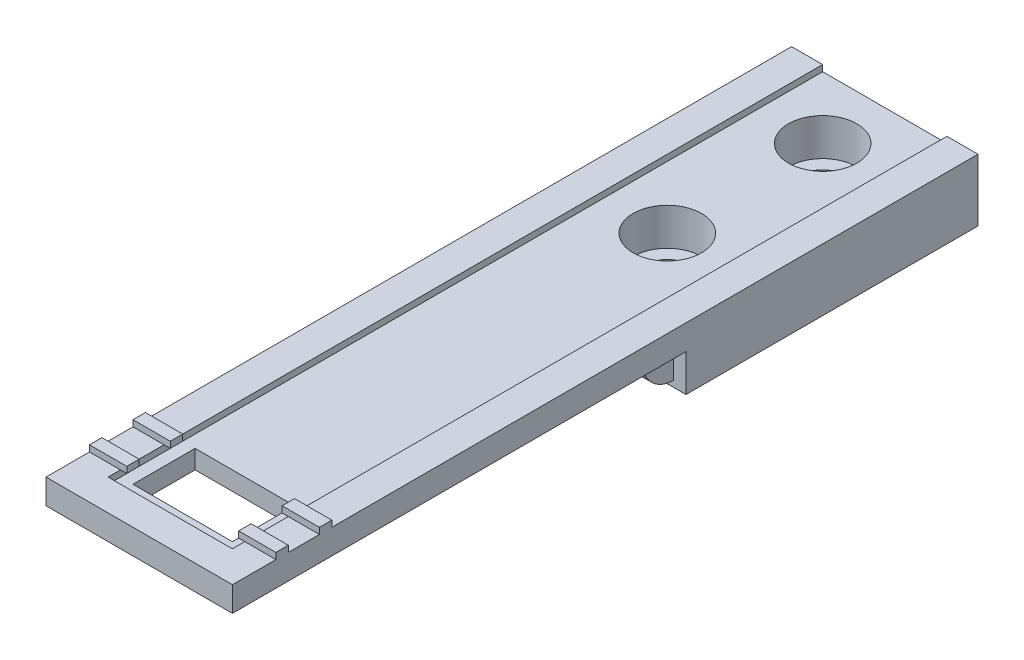
SolidWorks part; units mm, degrees
ref_plane "Front Plane" through (0, 0, 0) normal (0, 0, 1) x (1, 0, 0)
ref_plane "Top Plane" through (0, 0, 0) normal (0, 1, 0) x (1, 0, 0)
ref_plane "Right Plane" through (0, 0, 0) normal (1, 0, 0) x (0, 0, -1)
sketch "Sketch1" plane through (0, 0, 0) normal (0, 1, 0) x (1, 0, 0)
  line L1 (-12.8623, 1.9673) -> (17.1377, 1.9673)
  line L2 (-12.8623, 1.9673) -> (-12.8623, -118.0327)
  line L3 (-12.8623, -118.0327) -> (17.1377, -118.0327)
  line L4 (17.1377, 1.9673) -> (17.1377, -118.0327)
  dimension "D1" = 30
  dimension "D2" = 120
extrude "Boss-Extrude1" add sketch "Sketch1" along normal blind 9
sketch "Sketch2" plane through (0, 9, 0) normal (0, 1, 0) x (1, 0, 0)
  line L0 (17.1377, -118.0327) -> (17.1377, 1.9673) construction
  line L1 (-12.8623, -118.0327) -> (17.1377, -118.0327)
  line L2 (-12.8623, -118.0327) -> (-12.8623, -73.0327)
  line L3 (-7.8623, -113.0327) -> (12.1377, -113.0327)
  line L4 (17.1377, -118.0327) -> (17.1377, -68.0327)
  line L7 (-7.8623, -113.0327) -> (-7.8623, 1.9673)
  line L8 (-7.8623, 1.9673) -> (-12.8623, 1.9673)
  line L9 (-12.8623, -73.0327) -> (-12.8623, 1.9673)
  line L11 (12.1377, -113.0327) -> (12.1377, 1.9673)
  line L12 (12.1377, 1.9673) -> (17.1377, 1.9673)
  line L13 (17.1377, -68.0327) -> (17.1377, 1.9673)
  dimension "D1" = 5
  dimension "D2" = 20
extrude "Boss-Extrude2" add sketch "Sketch2" along normal blind 1
sketch "Sketch3" plane through (0, 9, 0) normal (0, 1, 0) x (1, 0, 0)
  circle A0 centre (57.1377, -38.0327) radius 3.25
  circle A2 centre (7.1377, -38.0327) radius 3.25
  circle A3 centre (32.1377, -38.0327) radius 3.25 [skipped]
  circle A4 centre (7.1377, -13.0327) radius 3.25
  circle A5 centre (57.1377, -13.0327) radius 3.25
  dimension "D1" = 6.5
  dimension "D2" = 3
  dimension "D3" = 2
extrude "Cut-Extrude1" [suppressed] cut sketch "Sketch3" against normal through all
sketch "Sketch4" plane through (0, 9, 0) normal (0, 1, 0) x (1, 0, 0)
  circle A2 centre (57.1377, -38.0327) radius 5.5
  circle A4 centre (57.1377, -13.0327) radius 5.5
  dimension "D3" = 2
extrude "Cut-Extrude2" [suppressed] cut sketch "Sketch4" against normal blind 7
sketch "Sketch5" plane through (0, 0, -1.9673) normal (0, 0, -1) x (-1, 0, 0)
  line L0 (-12.1377, 9) -> (7.8623, 9) construction
  line L1 (-15.6377, 9) -> (-13.6377, 9)
  line L2 (-15.6377, 9) -> (-19.6377, 5)
  line L3 (-19.6377, 5) -> (-9.6377, 5)
  line L4 (-13.6377, 9) -> (-9.6377, 5)
  line L5 (-2.1377, 0) -> (-2.1377, 10) construction
  line L6 (-17.1377, 0) -> (12.8623, 0) construction
  line L7 (-12.1377, 10) -> (7.8623, 10) construction
  line L8 (15.3623, 5) -> (5.3623, 5)
  line L9 (9.3623, 9) -> (5.3623, 5)
  line L10 (11.3623, 9) -> (9.3623, 9)
  line L11 (11.3623, 9) -> (15.3623, 5)
  line L12 (-70.1377, 3) -> (-68.1377, 3)
  line L13 (65.8623, 9) -> (63.8623, 9)
  line L14 (65.8623, 9) -> (65.8623, 3)
  line L15 (65.8623, 3) -> (63.8623, 3)
  line L16 (63.8623, 9) -> (63.8623, 3)
  line L17 (-68.1377, 9) -> (-68.1377, 3)
  line L18 (-70.1377, 9) -> (-68.1377, 9)
  line L19 (-70.1377, 9) -> (-70.1377, 3)
  line L20 (-12.1377, 9) -> (7.8623, 9) construction
  line L21 (-4.6377, 9) -> (0.3623, 9)
  line L22 (-4.6377, 9) -> (-4.6377, 4)
  line L23 (-4.6377, 4) -> (0.3623, 4)
  line L24 (0.3623, 9) -> (0.3623, 4)
  point P16 (10.3623, 5)
  point P17 (-14.6377, 5)
  point P37 (-2.1377, 4)
  dimension "D1" = 4
  dimension "D2" = 45
  dimension "D3" = 225
  dimension "D4" = 10
  dimension "D5" = 25
  dimension "D6" = 6
  dimension "D7" = 2
  dimension "D8" = 5
  dimension "D9" = 5
extrude "Cut-Extrude3" [suppressed] cut sketch "Sketch5" against normal up to surface (75 mm away)
fillet "Fillet2" [suppressed] radius 0.5
sketch "Sketch6" plane through (17.1377, 0, 0) normal (1, 0, 0) x (0, 0, -1)
  line L0 (-118.0327, 10) -> (1.9673, 10) construction
  line L1 (1.9673, 10) -> (1.9673, 0) construction
  circle A0 centre (-3.0327, 7.5) radius 1.5
  circle A1 centre (-13.0327, 7.5) radius 1.5
  circle A2 centre (-23.0327, 7.5) radius 1.5
  circle A3 centre (-33.0327, 7.5) radius 1.5
  circle A4 centre (-43.0327, 7.5) radius 1.5
  circle A5 centre (-53.0327, 7.5) radius 1.5
  circle A6 centre (-63.0327, 7.5) radius 1.5
  dimension "D1" = 3
  dimension "D2" = 2.5
  dimension "D3" = 5
  dimension "D4" = 7
extrude "Cut-Extrude4" [suppressed] cut sketch "Sketch6" against normal up to surface (7 mm away)
ref_axis "Axis1" through (2.1377, 0, -1.9673) along (0, -1, 0)
sketch "Sketch7" plane through (-12.8623, 0, 0) normal (-1, 0, 0) x (0, 0, 1)
  line L0 (-1.9673, 10) -> (-1.9673, 0) construction
  line L1 (-1.9673, 10) -> (118.0327, 10) construction
  circle A0 centre (3.0327, 6) radius 1.5
  circle A1 centre (13.0327, 6) radius 1.5
  circle A2 centre (23.0327, 6) radius 1.5
  circle A3 centre (33.0327, 6) radius 1.5
  circle A4 centre (43.0327, 6) radius 1.5
  circle A5 centre (53.0327, 6) radius 1.5
  circle A6 centre (63.0327, 6) radius 1.5
  dimension "D1" = 3
  dimension "D2" = 5
  dimension "D3" = 4
  dimension "D4" = 7
extrude "Cut-Extrude5" [suppressed] cut sketch "Sketch7" against normal up to surface (7 mm away)
sketch "Sketch8" [suppressed] plane through (0, 0, -1.9673) normal (0, 0, -1) x (-1, 0, 0)
  line L0 (-42.4306, 14) -> (-34.6377, 14) construction
  line L1 (-38.1377, 14) -> (-26.1377, 14)
  line L2 (-38.1377, 14) -> (-38.1377, 9)
  line L3 (-38.1377, 9) -> (-26.1377, 9)
  line L4 (-26.1377, 14) -> (-26.1377, 9)
  line L5 (-32.1377, 0) -> (-32.1377, -39.7373) construction
  line L6 (-34.6377, 9) -> (-29.6377, 9) construction
  point P8 (-32.1377, 9)
  dimension "D1" = 12
extrude "Cut-Extrude6" [suppressed] cut sketch "Sketch8" against normal blind 5
sketch "Sketch9" [suppressed] plane through (0, 9, 0) normal (0, 1, 0) x (1, 0, 0)
  line L0 (32.1377, 1.9673) -> (32.1377, -3.2829) construction
  line L1 (38.1377, 1.9673) -> (26.1377, 1.9673) construction
  line L2 (38.1377, -3.0327) -> (38.1377, 1.9673) construction
  circle A0 centre (36.1377, -0.5327) radius 1.75
  circle A1 centre (28.1377, -0.5327) radius 1.75
  point P11 (38.1377, -0.5327)
  dimension "D1" = 3.5
  dimension "D2" = 2
extrude "Cut-Extrude7" [suppressed] cut sketch "Sketch9" against normal through all
sketch "Sketch10" [suppressed] plane through (0, 0, 0) normal (0, -1, 0) x (1, 0, 0)
  circle A0 centre (36.1377, 0.5327) radius 3
  circle A2 centre (28.1377, 0.5327) radius 3.25
  dimension "D1" = 6
  dimension "D2" = 6.5
extrude "Cut-Extrude8" [suppressed] cut sketch "Sketch10" against normal blind 4
sketch "Sketch11" plane through (0, 9, 0) normal (0, 1, 0) x (1, 0, 0)
  line L0 (12.1377, -113.0327) -> (-7.8623, -113.0327) construction
  line L1 (-2.8623, -108.0327) -> (7.1377, -108.0327)
  line L2 (-2.8623, -108.0327) -> (-2.8623, -98.0327)
  line L3 (-2.8623, -98.0327) -> (7.1377, -98.0327)
  line L4 (7.1377, -108.0327) -> (7.1377, -98.0327)
  line L5 (2.1377, -69.8195) -> (2.1377, -53.1374) construction
  line L6 (12.1377, -113.0327) -> (-7.8623, -113.0327) construction
  line L8 (-2.8623, -108.0327) -> (-2.8623, -98.0327)
  line L9 (7.1377, -98.0327) -> (-2.8623, -98.0327)
  line L10 (7.1377, -108.0327) -> (7.1377, -98.0327)
  line L11 (7.1377, -108.0327) -> (-2.8623, -108.0327)
  point P6 (2.1377, -113.0327)
  point P7 (2.1377, -108.0327)
  point P13 (2.1377, -113.0327)
  dimension "D1" = 10
  dimension "D2" = 10
  dimension "D3" = 5
extrude "Cut-Extrude10" [suppressed] cut sketch "Sketch11" against normal through all
sketch "Sketch12" plane through (0, 9, 0) normal (0, 1, 0) x (1, 0, 0)
  line L0 (2.1377, 1.9673) -> (2.1377, -113.0327) construction
  line L1 (12.1377, -113.0327) -> (-7.8623, -113.0327) construction
  line L2 (12.1377, 1.9673) -> (-7.8623, 1.9673) construction
  point P5 (2.1377, -8.0327)
  point P6 (2.1377, -33.0327)
  point P7 (0, 0)
  point P8 (0, 0)
  dimension "D1" = 25
  dimension "D2" = 10
hole_wizard "CBORE for M6 Hex Socket Head Cap1" positions "Sketch15" profile "Sketch16" counterbore size "M6" standard "BSI" end condition up to next
sketch "Sketch15" plane through (0, 9, 0) normal (0, 1, 0) x (1, 0, 0)
  point P0 (2.1377, -8.0327)
  point P3 (2.1377, -33.0327)
sketch "Sketch16" plane through (2.1377, 9, 8.0327) normal (1, 0, 0) x (0, 0, 1)
  line L0 (0, 0) -> (0, 9)
  line L1 (0, 9) -> (3.3, 9)
  line L3 (3.3, 9) -> (3.3, 6)
  line L4 (3.3, 6) -> (5.5, 6)
  line L5 (5.5, 6) -> (5.5, 0)
  line L7 (5.5, 0) -> (0, 0)
  line L11 (0, -6.35) -> (0, 107.95) construction
  dimension "Thru Hole Dia." = 6.6
  dimension "Thru Hole Depth" = 9
  dimension "C'Bore Dia." = 11
  dimension "C'Bore Depth" = 6
sketch "Sketch17" plane through (0, 10, 0) normal (0, 1, 0) x (1, 0, 0)
  line L0 (2.1377, -118.0327) -> (2.1377, 1.9673) construction
  line L1 (17.1377, -111.0327) -> (11.1377, -111.0327)
  line L2 (17.1377, -111.0327) -> (17.1377, -109.0327)
  line L3 (17.1377, -109.0327) -> (11.1377, -109.0327)
  line L4 (11.1377, -111.0327) -> (11.1377, -109.0327)
  line L5 (-12.8623, -118.0327) -> (17.1377, -118.0327) construction
  line L6 (17.1377, -118.0327) -> (17.1377, 1.9673) construction
  line L7 (12.1377, -113.0327) -> (-7.8623, -113.0327) construction
  line L8 (12.1377, 1.9673) -> (12.1377, -113.0327) construction
  line L9 (-6.8623, -111.0327) -> (-6.8623, -109.0327)
  line L10 (-12.8623, -109.0327) -> (-6.8623, -109.0327)
  line L11 (-12.8623, -111.0327) -> (-12.8623, -109.0327)
  line L12 (-12.8623, -111.0327) -> (-6.8623, -111.0327)
  line L13 (17.1377, -104.0327) -> (11.1377, -104.0327)
  line L14 (17.1377, -104.0327) -> (17.1377, -102.0327)
  line L15 (17.1377, -102.0327) -> (11.1377, -102.0327)
  line L16 (11.1377, -104.0327) -> (11.1377, -102.0327)
  line L17 (-6.8623, -104.0327) -> (-6.8623, -102.0327)
  line L18 (-12.8623, -102.0327) -> (-6.8623, -102.0327)
  line L19 (-12.8623, -104.0327) -> (-12.8623, -102.0327)
  line L20 (-12.8623, -104.0327) -> (-6.8623, -104.0327)
  dimension "D1" = 2
  dimension "D2" = 2
  dimension "D3" = 1
  dimension "D4" = 2
extrude "Boss-Extrude3" add sketch "Sketch17" along normal blind 1
sketch "Sketch18" plane through (0, 9, 0) normal (0, 1, 0) x (1, 0, 0)
  line L0 (2.1377, 1.9673) -> (2.1377, -113.0327) construction
  line L1 (10.1377, -101.0327) -> (-5.8623, -101.0327)
  line L2 (10.1377, -101.0327) -> (10.1377, -111.0327)
  line L3 (10.1377, -111.0327) -> (-5.8623, -111.0327)
  line L4 (-5.8623, -101.0327) -> (-5.8623, -111.0327)
  line L5 (12.1377, -113.0327) -> (-7.8623, -113.0327) construction
  line L6 (12.1377, 1.9673) -> (12.1377, -113.0327) construction
  point P6 (2.1377, -111.0327)
  dimension "D1" = 2
  dimension "D2" = 2
  dimension "D3" = 10
extrude "Cut-Extrude11" cut sketch "Sketch18" against normal through all and the other way through all
sketch "Sketch19" plane through (0, 0, 0) normal (0, -1, 0) x (1, 0, 0)
  line L0 (-12.8623, -1.9673) -> (-12.8623, 118.0327) construction
  line L1 (17.1377, 118.0327) -> (-12.8623, 118.0327)
  line L2 (17.1377, 118.0327) -> (17.1377, 45.0327)
  line L3 (17.1377, 45.0327) -> (-12.8623, 45.0327)
  line L4 (-12.8623, 118.0327) -> (-12.8623, 45.0327)
  dimension "D1" = 12
extrude "Cut-Extrude12" cut sketch "Sketch19" against normal blind 6
sketch "Sketch20" plane through (0, 6, 0) normal (0, -1, 0) x (1, 0, 0)
  line L0 (-12.8623, 45.0327) -> (17.1377, 45.0327) construction
  line L1 (-10.8623, 45.0327) -> (-8.8623, 45.0327)
  line L2 (-10.8623, 45.0327) -> (-10.8623, 50.0327)
  line L3 (-10.8623, 50.0327) -> (-8.8623, 50.0327)
  line L4 (-8.8623, 45.0327) -> (-8.8623, 50.0327)
  line L5 (-12.8623, 118.0327) -> (-12.8623, 45.0327) construction
  line L6 (2.1377, 118.0327) -> (2.1377, 45.0327) construction
  line L7 (17.1377, 118.0327) -> (-12.8623, 118.0327) construction
  line L8 (13.1377, 45.0327) -> (13.1377, 50.0327)
  line L9 (15.1377, 50.0327) -> (13.1377, 50.0327)
  line L10 (15.1377, 45.0327) -> (15.1377, 50.0327)
  line L11 (15.1377, 45.0327) -> (13.1377, 45.0327)
  dimension "D1" = 5
  dimension "D2" = 2
  dimension "D3" = 2
revolve "Revolve2" add sketch "Sketch20" angle 90 about axis through (17.1377, 6, 45.0327) along (1, 0, 0)
